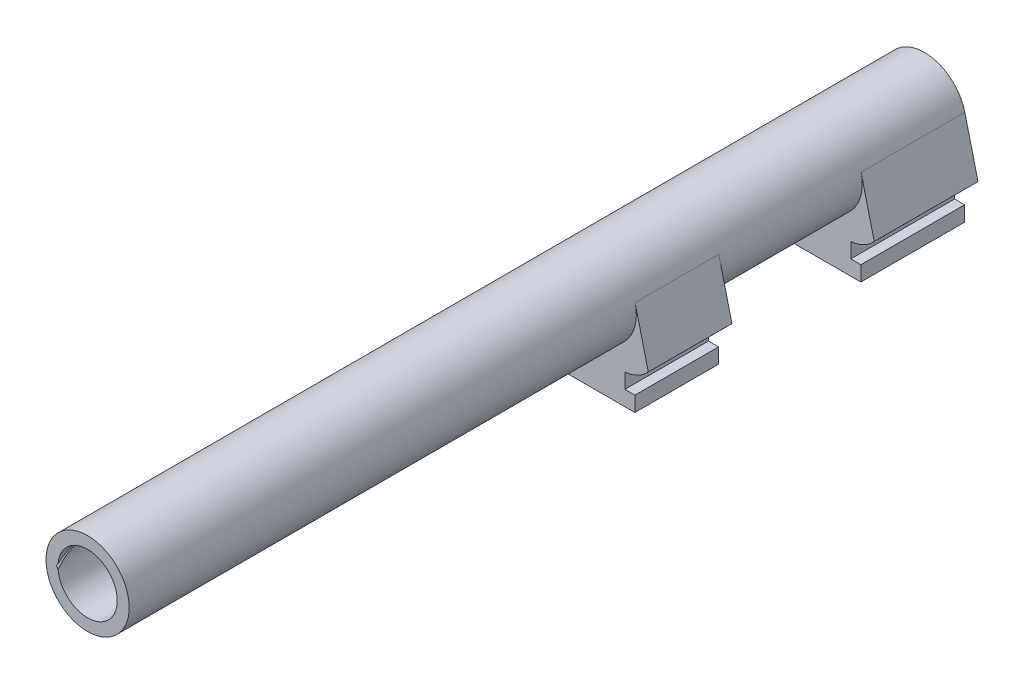
SolidWorks part; units mm, degrees
material "Brass"
ref_plane "Front Plane" through (0, 0, 0) normal (0, 0, 1) x (1, 0, 0)
ref_plane "Top Plane" through (0, 0, 0) normal (0, 1, 0) x (1, 0, 0)
ref_plane "Right Plane" through (0, 0, 0) normal (1, 0, 0) x (0, 0, -1)
sketch "Sketch1" plane through (0, 0, 0) normal (0, 0, 1) x (1, 0, 0)
  circle A0 centre (0, 0) radius 4.5
  circle A1 centre (0, 0) radius 6.3112
  dimension "D1" = 9
  dimension "D2" = 12.6225
extrude "Boss-Extrude1" add sketch "Sketch1" along normal blind 127
sketch "Sketch2" plane through (0, 0, 0) normal (0, 0, -1) x (-1, 0, 0)
  line L0 (0, 0) -> (0, 19.9189) construction
  line L4 (-6.096, -12.954) -> (6.096, -12.954)
  line L15 (0, -6.3112) -> (0, -12.954)
  line L16 (8.128, -6.604) -> (-8.128, -6.604)
  line L17 (-6.096, -12.954) -> (6.096, -12.954)
  line L19 (-6.096, -12.954) -> (-6.096, -10.668)
  line L20 (-6.096, -10.668) -> (6.096, -10.668)
  line L21 (0, -12.954) -> (0, -10.668)
  line L22 (-4.572, -10.668) -> (4.572, -10.668)
  line L23 (-4.572, -10.668) -> (-4.572, -8.382)
  line L24 (-4.572, -8.382) -> (4.572, -8.382)
  line L25 (0, -10.668) -> (0, -8.382)
  line L26 (-8.128, -6.604) -> (-6.1278, 1.5105)
  line L27 (8.128, -6.604) -> (6.1278, 1.5105)
  line L28 (4.572, -10.668) -> (4.572, -8.382)
  line L29 (6.096, -12.954) -> (6.096, -10.668)
  arc A0 (8.128, -6.604) -> (4.572, -8.382) centre (4.1364, -3.0658) cw
  arc A2 (-8.128, -6.604) -> (-4.572, -8.382) centre (-4.1364, -3.0658) ccw
  circle A3 centre (0, 0) radius 6.3112 construction
  point P24 (0, -6.604)
  circle M20 centre (0, 0) radius 6.3112
  dimension "D8" = 5.334
  dimension "D1" = 12.954
  dimension "D2" = 6.096
  dimension "D3" = 2.286
  dimension "D4" = 2.286
  dimension "D5" = 4.572
  dimension "D6" = 8.128
  dimension "D7" = 1.778
extrude "Boss-Extrude2" add sketch "Sketch2" against normal blind 15.748 contours L15 | M20 | L15 | M20 | L15 | L15 L20 | L15 L20 L4 | L15 L4 L20 region at (3.048, -11.811, 0) region at (-3.048, -11.811, 0) region at (2.286, -9.525, 0) region at (-2.286, -9.525, 0) region at (3.5213, -7.4284, 0) region at (-3.5213, -7.4284, 0) region at (5.5033, -4.7666, 0) region at (-5.5033, -4.7666, 0)
extrude "Boss-Extrude3" add sketch "Sketch2<5>" against normal blind 12.7 from offset 37.338 contours M20 | L15 | L15 L20 | L15 L20 L4 | L15 L4 L20 | L15 | L15 | M20 region at (3.048, -11.811, 0) region at (-3.048, -11.811, 0) region at (2.286, -9.525, 0) region at (-2.286, -9.525, 0) region at (3.5213, -7.4284, 0) region at (-3.5213, -7.4284, 0) region at (5.5033, -4.7666, 0) region at (-5.5033, -4.7666, 0) offset against normal yes
sketch "Sketch2<5>" plane through (0, 0, 0) normal (0, 0, -1) x (-1, 0, 0) same geometry as "Sketch2"
sketch "Sketch4" plane through (0, 0, 127) normal (0, 0, 1) x (1, 0, 0)
  circle A1 centre (0, 0) radius 4.5
  circle A2 centre (0, 0) radius 4.5 construction
curve "Helix/Spiral1" pitch 25.4 height 127 radius 4.5 centre (0, 0, 127) axis (0, 0, -1) start towards (-1, 0, 0)
sketch "Sketch5" plane through (0, 0, 127) normal (0, 0, 1) x (1, 0, 0)
  line L0 (-4.4838, -0.381) -> (-4.7273, 0)
  line L1 (-4.7273, 0) -> (-4.4838, 0.381)
  line L3 (-4.4838, 0.381) -> (-4.1949, 0.381)
  line L5 (-4.4838, -0.381) -> (-4.1949, -0.381)
  line L6 (-4.1949, 0.381) -> (-4.1949, -0.381)
  circle A0 centre (0, 0) radius 4.5 construction
  point P7 (-4.7273, 0)
  dimension "D1" = 0.762
sweep "Cut-Sweep1" cut profiles "Sketch5" path "Helix/Spiral1" align with end faces yes
